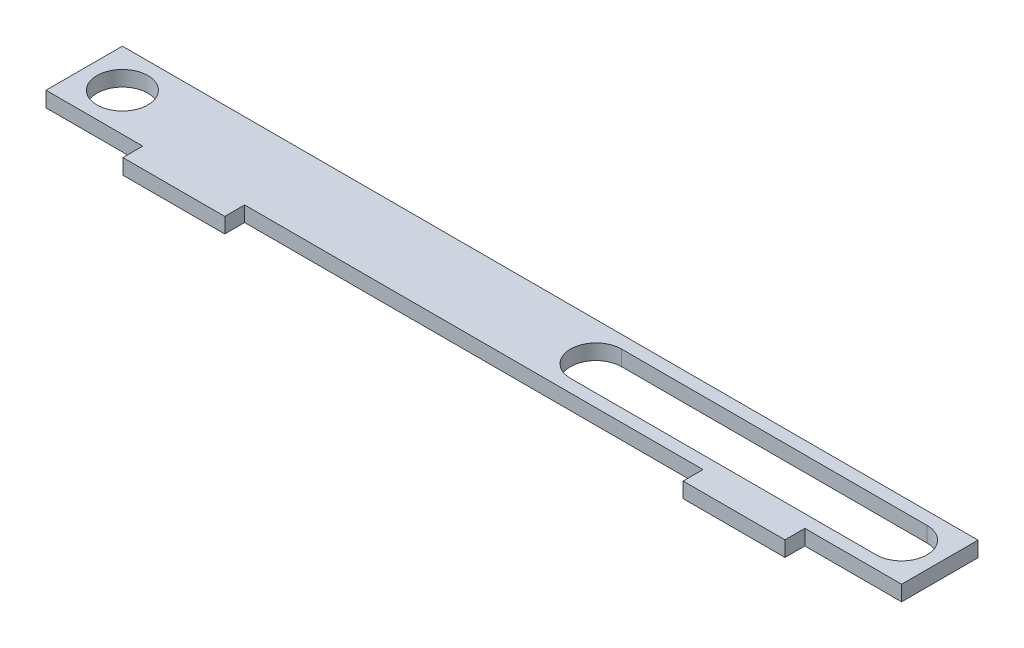
SolidWorks part; units mm, degrees
material "Acrylic (Medium-high impact)"
ref_plane "Front Plane" through (0, 0, 0) normal (0, 0, 1) x (1, 0, 0)
ref_plane "Top Plane" through (0, 0, 0) normal (0, 1, 0) x (1, 0, 0)
ref_plane "Right Plane" through (0, 0, 0) normal (1, 0, 0) x (0, 0, -1)
sketch "Sketch1" plane through (0, 0, 0) normal (0, 1, 0) x (1, 0, 0)
  line L0 (160.5, 7.5) -> (100.5, 7.5) construction
  line L1 (0, 0) -> (19, 0)
  line L2 (0, 0) -> (0, 15)
  line L3 (0, 15) -> (168, 15)
  line L4 (168, 0) -> (168, 15)
  line L5 (160.5, 2.5) -> (100.5, 2.5)
  line L6 (160.5, 12.5) -> (100.5, 12.5)
  line L7 (84, 15) -> (84, 0) construction
  line L9 (19, 0) -> (19, -3.9)
  line L10 (19, -3.9) -> (39, -3.9)
  line L11 (39, 0) -> (39, -3.9)
  line L12 (149, -3.9) -> (129, -3.9)
  line L13 (129, 0) -> (129, -3.9)
  line L15 (149, 0) -> (149, -3.9)
  line L16 (39, 0) -> (129, 0)
  line L17 (149, 0) -> (168, 0)
  circle A1 centre (7.5, 7.5) radius 5
  arc A2 (160.5, 2.5) -> (160.5, 12.5) centre (160.5, 7.5) ccw
  arc A3 (100.5, 12.5) -> (100.5, 2.5) centre (100.5, 7.5) ccw
  point P9 (130.5, 7.5)
  dimension "D3" = 10
  dimension "D7" = 5
  dimension "D1" = 168
  dimension "D2" = 15
  dimension "D4" = 7.5
  dimension "D5" = 7.5
  dimension "D6" = 7.5
  dimension "D8" = 60
  dimension "D9" = 3.9
  dimension "D10" = 20
  dimension "D11" = 45
extrude "Boss-Extrude1" add sketch "Sketch1" along normal blind 3
